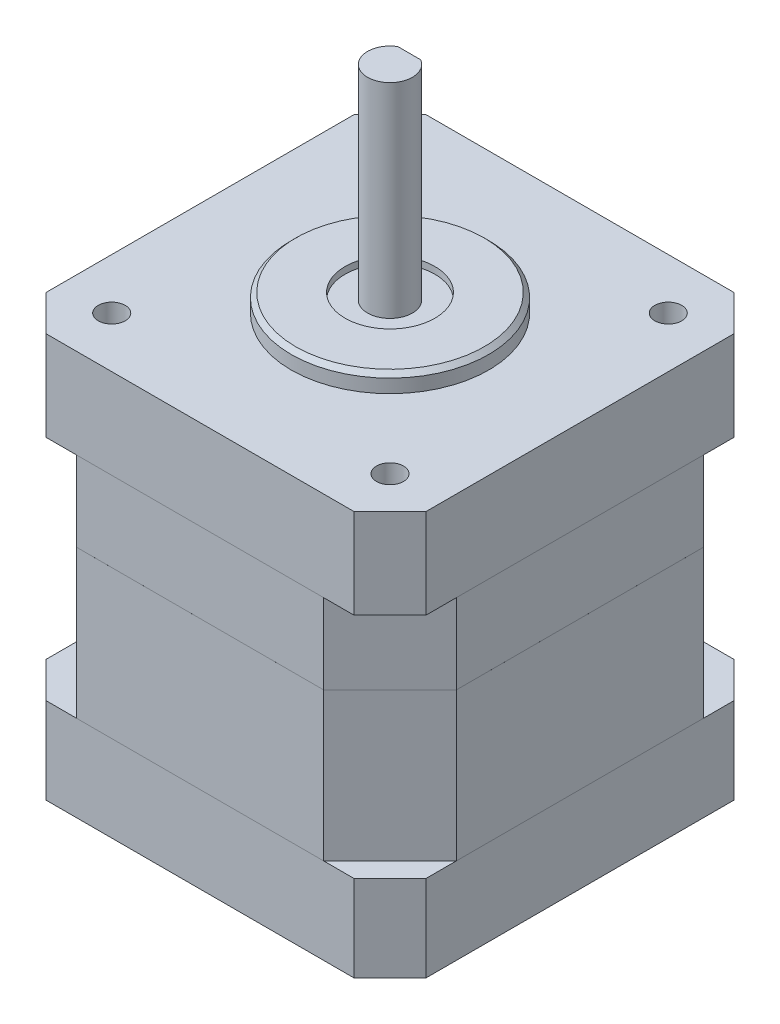
SolidWorks part; units mm, degrees
ref_plane "Front" through (0, 0, 0) normal (0, 0, 1) x (1, 0, 0)
ref_plane "Top" through (0, 0, 0) normal (0, 1, 0) x (1, 0, 0)
ref_plane "Right" through (0, 0, 0) normal (1, 0, 0) x (0, 0, -1)
sketch "Sketch1" plane through (0, 0, 0) normal (0, 1, 0) x (1, 0, 0)
  line L1 (-21.15, 21.15) -> (21.15, 21.15)
  line L2 (-21.15, 21.15) -> (-21.15, -21.15)
  line L3 (-21.15, -21.15) -> (21.15, -21.15)
  line L4 (21.15, 21.15) -> (21.15, -21.15)
  line L7 (0, 20) -> (0, -20) construction
  line L8 (20, 0) -> (-20, 0) construction
  line L10 (-55, 0) -> (55, 0) construction
  line L11 (0, -55) -> (0, 55) construction
  dimension "D1" = 42.3
extrude "Extrude1" add sketch "Sketch1" along normal blind 9.6 from offset 17 offset against normal yes
chamfer "Chamfer3" distance 4 angle 45 4 edges at (21.15, -12.2, 21.15) (-21.15, -12.2, 21.15) (21.15, -12.2, -21.15) (-21.15, -12.2, -21.15)
sketch "Sketch31" plane through (0, -7.4, 0) normal (0, 1, 0) x (1, 0, 0)
  line L0 (0, 21.15) -> (-13.75, 21.15) construction
  line L1 (17.15, 21.15) -> (-17.15, 21.15) construction
  line L2 (-13.75, 21.15) -> (13.75, 21.15)
  line L3 (-13.75, 21.15) -> (-21.15, 13.75)
  line L4 (-21.15, 17.15) -> (-21.15, -17.15) construction
  line L5 (13.75, 21.15) -> (21.15, 13.75)
  line L6 (21.15, -17.15) -> (21.15, 17.15) construction
  line L7 (-21.15, 0) -> (21.15, 0) construction
  line L8 (0, -21.15) -> (-13.75, -21.15) construction
  line L9 (13.75, -21.15) -> (21.15, -13.75)
  line L10 (-13.75, -21.15) -> (-21.15, -13.75)
  line L11 (-13.75, -21.15) -> (13.75, -21.15)
  line L12 (-21.15, 13.75) -> (-21.15, -13.75)
  line L13 (21.15, 13.75) -> (21.15, -13.75)
  dimension "D1" = 13.75
  dimension "D2" = 27.5
  dimension "D3" = 10.4652
extrude "Boss-Extrude8" add sketch "Sketch31" along normal blind 16.5
sketch "Sketch32" plane through (0, 9.1, 0) normal (0, 1, 0) x (1, 0, 0)
  line L0 (-17.15, 21.15) -> (-21.15, 17.15) construction
  line L1 (-13.75, 21.15) -> (-17.15, 21.15) construction
  line L2 (13.75, 21.15) -> (-13.75, 21.15) construction
  line L3 (17.15, 21.15) -> (13.75, 21.15) construction
  line L4 (21.15, 17.15) -> (17.15, 21.15) construction
  line L5 (21.15, 13.75) -> (21.15, 17.15) construction
  line L6 (21.15, -13.75) -> (21.15, 13.75) construction
  line L7 (-21.15, 17.15) -> (-21.15, 13.75) construction
  line L8 (-21.15, 13.75) -> (-21.15, -13.75) construction
  line L9 (21.15, -17.15) -> (21.15, -13.75) construction
  line L10 (17.15, -21.15) -> (21.15, -17.15) construction
  line L11 (13.75, -21.15) -> (17.15, -21.15) construction
  line L12 (-13.75, -21.15) -> (13.75, -21.15) construction
  line L13 (-17.15, -21.15) -> (-13.75, -21.15) construction
  line L14 (-21.15, -17.15) -> (-17.15, -21.15) construction
  line L15 (-21.15, -13.75) -> (-21.15, -17.15) construction
  line L16 (-17.15, 21.15) -> (-21.15, 17.15)
  line L17 (-13.75, 21.15) -> (-17.15, 21.15)
  line L18 (13.75, 21.15) -> (-13.75, 21.15)
  line L19 (17.15, 21.15) -> (13.75, 21.15)
  line L20 (21.15, 17.15) -> (17.15, 21.15)
  line L21 (21.15, 13.75) -> (21.15, 17.15)
  line L22 (21.15, -13.75) -> (21.15, 13.75)
  line L23 (-21.15, 17.15) -> (-21.15, 13.75)
  line L24 (-21.15, 13.75) -> (-21.15, -13.75)
  line L25 (21.15, -17.15) -> (21.15, -13.75)
  line L26 (17.15, -21.15) -> (21.15, -17.15)
  line L27 (13.75, -21.15) -> (17.15, -21.15)
  line L28 (-13.75, -21.15) -> (13.75, -21.15)
  line L29 (-17.15, -21.15) -> (-13.75, -21.15)
  line L30 (-21.15, -17.15) -> (-17.15, -21.15)
  line L31 (-21.15, -13.75) -> (-21.15, -17.15)
extrude "Boss-Extrude9" add sketch "Sketch32" along normal blind 7.65
sketch "Sketch33" plane through (0, 16.75, 0) normal (0, 1, 0) x (1, 0, 0)
  line L0 (-19.15, 19.15) -> (19.15, -19.15) construction
  line L1 (-17.15, 21.15) -> (-21.15, 17.15) construction
  line L2 (17.15, -21.15) -> (21.15, -17.15) construction
  circle A0 centre (0, 0) radius 11
  dimension "D1" = 22
extrude "Boss-Extrude10" add sketch "Sketch33" along normal blind 2
sketch "Sketch34" plane through (0, 18.75, 0) normal (0, 1, 0) x (1, 0, 0)
  circle A0 centre (0, 0) radius 5
  dimension "D1" = 10
extrude "Cut-Extrude1" cut sketch "Sketch34" against normal blind 2
sketch "Sketch35" plane through (0, 16.75, 0) normal (0, 1, 0) x (1, 0, 0)
  circle A0 centre (0, 0) radius 2.5
  dimension "D1" = 5
extrude "Boss-Extrude11" add sketch "Sketch35" along normal blind 20
sketch "Sketch36" plane through (0, 36.75, 0) normal (0, 1, 0) x (1, 0, 0)
  line L0 (0, -2.5) -> (0, 2.15)
  line L1 (-1.2757, 2.15) -> (1.2757, 2.15)
  circle A0 centre (0, 0) radius 2.5 construction
  circle A1 centre (0, 0) radius 2.5 construction
  circle A2 centre (0, 0) radius 2.5
  circle M1 centre (0, 0) radius 2.5
  dimension "D1" = 4.65
extrude "Cut-Extrude3" cut sketch "Sketch36" against normal blind 15 contours L1 M1 region at (0, 36.75, -2.2909)
sketch "Sketch37" plane through (21.15, 0, 0) normal (1, 0, 0) x (0, 0, -1)
  line L0 (-13.75, 9.1) -> (13.75, 9.1)
  line L1 (13.75, 9.1) -> (13.75, -7.4)
  line L2 (13.75, -7.4) -> (-13.75, -7.4)
  line L3 (-13.75, -7.4) -> (-13.75, 9.1)
extrude "Boss-Extrude12" add sketch "Sketch37" along normal blind 0.001
sketch "Sketch38" plane through (0, 0, 21.15) normal (0, 0, 1) x (1, 0, 0)
  line L1 (-13.75, 9.1) -> (13.75, 9.1)
  line L2 (-13.75, 9.1) -> (-13.75, -7.4)
  line L3 (-13.75, -7.4) -> (13.75, -7.4)
  line L4 (13.75, 9.1) -> (13.75, -7.4)
extrude "Boss-Extrude13" add sketch "Sketch38" along normal blind 0.001
sketch "Sketch39" plane through (-21.15, 0, 0) normal (-1, 0, 0) x (0, 0, 1)
  line L1 (-13.75, 9.1) -> (13.75, 9.1)
  line L2 (-13.75, 9.1) -> (-13.75, -7.4)
  line L3 (-13.75, -7.4) -> (13.75, -7.4)
  line L4 (13.75, 9.1) -> (13.75, -7.4)
extrude "Boss-Extrude14" add sketch "Sketch39" along normal blind 0.001
sketch "Sketch40" plane through (0, 0, -21.15) normal (0, 0, -1) x (-1, 0, 0)
  line L1 (-13.75, 9.1) -> (13.75, 9.1)
  line L2 (-13.75, 9.1) -> (-13.75, -7.4)
  line L3 (-13.75, -7.4) -> (13.75, -7.4)
  line L4 (13.75, 9.1) -> (13.75, -7.4)
extrude "Boss-Extrude15" add sketch "Sketch40" along normal blind 0.001
sketch "Sketch41" plane through (0, 16.75, 0) normal (0, 1, 0) x (1, 0, 0)
  line L0 (0, 21.15) -> (0, -21.15) construction
  line L1 (-21.15, 17.15) -> (-21.15, -17.15) construction
  line L2 (-21.15, 0) -> (-15.5, 0) construction
  line L3 (-15.5, 0) -> (-15.5, 15.5) construction
  line L4 (17.15, 21.15) -> (-17.15, 21.15) construction
  line L5 (-17.15, -21.15) -> (17.15, -21.15) construction
  circle A0 centre (-15.5, 15.5) radius 1.5
  circle A1 centre (-15.5, -15.5) radius 1.5
  circle A2 centre (15.5, -15.5) radius 1.5
  circle A3 centre (15.5, 15.5) radius 1.5
  dimension "D1" = 3
  dimension "D2" = 15.5
  dimension "D3" = 5.65
extrude "Cut-Extrude4" cut sketch "Sketch41" against normal blind 6
sketch "Sketch42" plane through (0, -17, 0) normal (0, -1, 0) x (1, 0, 0)
  circle A0 centre (0, 0) radius 4.5
  circle A1 centre (-15.5, 15.5) radius 1.5 construction
  circle A2 centre (15.5, 15.5) radius 1.5 construction
  circle A3 centre (15.5, -15.5) radius 1.5 construction
  circle A4 centre (-15.5, -15.5) radius 1.5 construction
  circle A5 centre (-15.5, 15.5) radius 1.5
  circle A6 centre (15.5, 15.5) radius 1.5
  circle A7 centre (15.5, -15.5) radius 1.5
  circle A8 centre (-15.5, -15.5) radius 1.5
  dimension "D1" = 9
extrude "Cut-Extrude5" cut sketch "Sketch42" against normal blind 3
sketch "Sketch43" plane through (0, -17, 0) normal (0, -1, 0) x (1, 0, 0)
  line L0 (0, 21.15) -> (8, 21.15) construction
  line L1 (-17.15, 21.15) -> (17.15, 21.15) construction
  line L3 (8, 21.15) -> (-8, 21.15)
  line L4 (8, 21.15) -> (8, 25.15)
  line L5 (8, 25.15) -> (-8, 25.15)
  line L6 (-8, 21.15) -> (-8, 25.15)
  dimension "D1" = 8
  dimension "D2" = 16
  dimension "D3" = 4
extrude "Boss-Extrude16" add sketch "Sketch43" against normal blind 3.2
sketch "Sketch44" plane through (0, 0, 21.15) normal (0, 0, 1) x (1, 0, 0)
  line L1 (8, -13.8) -> (-8, -13.8)
  line L2 (8, -13.8) -> (8, -7.4)
  line L3 (8, -7.4) -> (-8, -7.4)
  line L4 (-8, -13.8) -> (-8, -7.4)
  dimension "D1" = 16
  dimension "D2" = 6.4
extrude "Boss-Extrude17" add sketch "Sketch44" along normal blind 6
sketch "Sketch45" plane through (0, 0, 27.15) normal (0, 0, 1) x (1, 0, 0)
  line L0 (-8, -7.4) -> (-7.5, -7.4) construction
  line L1 (8, -7.4) -> (-8, -7.4) construction
  line L2 (-7.5, -7.4) -> (-7.5, -7.9) construction
  line L4 (-7.5, -7.9) -> (7.5, -7.9)
  line L5 (-7.5, -7.9) -> (-7.5, -13.4)
  line L6 (-7.5, -13.4) -> (7.5, -13.4)
  line L7 (7.5, -7.9) -> (7.5, -13.4)
  dimension "D1" = 0.5
  dimension "D2" = 0.5
  dimension "D3" = 5.5
  dimension "D4" = 15
extrude "Cut-Extrude6" cut sketch "Sketch45" against normal blind 5
sketch "Sketch46" plane through (0, 10.75, 0) normal (0, 1, 0) x (1, 0, 0)
  circle A0 centre (-15.5, -15.5) radius 1.5
  circle A1 centre (-15.5, 15.5) radius 1.5 construction
  circle A2 centre (15.5, 15.5) radius 1.5 construction
  circle A3 centre (15.5, -15.5) radius 1.5 construction
  circle A4 centre (-15.5, 15.5) radius 1.5
  circle A5 centre (15.5, 15.5) radius 1.5
  circle A6 centre (15.5, -15.5) radius 1.5
extrude "Boss-Extrude18" add sketch "Sketch46" along normal blind 1.5
chamfer "Chamfer4" distance 0.4 angle 45 1 edges at (0, 18.75, 11)
sketch "草图2" plane through (0, 36.75, 0) normal (0, 1, 0) x (1, 0, 0)
  line L0 (-1.2757, 2.15) -> (1.2757, 2.15)
  line L1 (-1.2757, 2.15) -> (1.2757, 2.15) construction
  circle A0 centre (0, 0) radius 2.5
  line M1 (1.2757, 2.15) -> (-1.2757, 2.15)
  arc M2 (-1.2757, 2.15) -> (1.2757, 2.15) centre (0, 0) ccw
extrude "凸台-拉伸1" add sketch "草图2" along normal blind 15.25 contours M2 M1 region at (0, 36.75, 0.0727)
sketch "草图3" plane through (0, 21.75, 0) normal (0, 1, 0) x (1, 0, 0)
  circle A0 centre (0, 0) radius 2.5
extrude "凸台-拉伸2" add sketch "草图3" along normal blind 11.25
sketch "草图4" plane through (0, 16.75, 0) normal (0, 1, 0) x (1, 0, 0)
  circle A0 centre (0, 0) radius 11
  circle A1 centre (0, 0) radius 5
extrude "凸台-拉伸3" add sketch "草图4" along normal blind 13.25
chamfer "倒角1" distance 0.5 angle 45 1 edges at (0, 30, 11)
sketch "草图5" plane through (0, 16.75, 0) normal (0, 1, 0) x (1, 0, 0)
  line L0 (-17.15, -21.15) -> (-21.15, -17.15)
  line L1 (-21.15, -17.15) -> (-21.15, 17.15)
  line L2 (-21.15, 17.15) -> (-17.15, 21.15)
  line L3 (-17.15, 21.15) -> (17.15, 21.15)
  line L4 (17.15, 21.15) -> (21.15, 17.15)
  line L5 (21.15, 17.15) -> (21.15, -17.15)
  line L6 (21.15, -17.15) -> (17.15, -21.15)
  line L7 (17.15, -21.15) -> (-17.15, -21.15)
  line L8 (0, 0) -> (-15.5, 0)
  line L9 (-15.5, 0) -> (-15.5, 15.5)
  line L10 (-15.5, 15.5) -> (15.5, 15.5)
  line L11 (15.5, 15.5) -> (15.5, -15.5)
  line L12 (15.5, -15.5) -> (-15.5, -15.5)
  line L13 (-15.5, -15.5) -> (-15.5, 0)
  circle A0 centre (-15.5, -15.5) radius 1.5
  circle A1 centre (-15.5, 15.5) radius 1.5
  circle A2 centre (15.5, 15.5) radius 1.5
  circle A3 centre (15.5, -15.5) radius 1.5
  circle A4 centre (-15.5, -15.5) radius 1.5 construction
  circle A5 centre (15.5, -15.5) radius 1.5 construction
  circle A6 centre (-15.5, 15.5) radius 1.5 construction
  line M5 (17.15, 21.15) -> (-17.15, 21.15)
  line M6 (-17.15, 21.15) -> (-21.15, 17.15)
  line M7 (-21.15, 17.15) -> (-21.15, -17.15)
  line M8 (-21.15, -17.15) -> (-17.15, -21.15)
  line M9 (-17.15, -21.15) -> (17.15, -21.15)
  line M10 (17.15, -21.15) -> (21.15, -17.15)
  line M11 (21.15, -17.15) -> (21.15, 17.15)
  line M12 (21.15, 17.15) -> (17.15, 21.15)
  circle M13 centre (0, 0) radius 11
  dimension "D1" = 3
  dimension "D2" = 3
  dimension "D3" = 3
  dimension "D4" = 3
extrude "凸台-拉伸4" add sketch "草图5" along normal blind 11.25 contours A3 L12 A0 L13 L9 A1 L10 A2 L11 M12 M5 M6 M7 M8 M9 M10 M11 | A3 L11 A2 L10 A1 L9 L13 A0 L12 M13 region at (-18.727, 16.75, 18.727) region at (-15.0616, 16.75, -7)
sketch "草图8" plane through (0, 9.1, 0) normal (0, -1, 0) x (1, 0, 0)
  line L0 (-17.15, 21.15) -> (-21.15, 17.15)
  line L1 (-21.15, 17.15) -> (-21.15, -17.15)
  line L2 (-21.15, -17.15) -> (-17.15, -21.15)
  line L3 (-17.15, -21.15) -> (17.15, -21.15)
  line L4 (17.15, -21.15) -> (21.15, -17.15)
  line L5 (21.15, -17.15) -> (21.15, 17.15)
  line L6 (21.15, 17.15) -> (17.15, 21.15)
  line L7 (17.15, 21.15) -> (-17.15, 21.15)
extrude "切除-拉伸1" cut sketch "草图8" against normal blind 8.9
sketch "草图12" plane through (0, 9.1, 0) normal (0, 1, 0) x (1, 0, 0)
  line L0 (21.15, -13.75) -> (13.75, -21.151)
  line L1 (13.75, -21.151) -> (-13.75, -21.15)
  line L2 (-13.75, -21.15) -> (-21.15, -13.75)
  line L3 (-21.15, -13.75) -> (-21.151, 13.75)
  line L4 (-21.151, 13.75) -> (-13.75, 21.15)
  line L5 (-13.75, 21.15) -> (13.75, 21.151)
  line L6 (13.75, 21.151) -> (21.151, 13.75)
  line L7 (21.151, 13.75) -> (21.15, -13.75)
extrude "凸台-拉伸8" add sketch "草图12" along normal blind 8.9
sketch "草图13" plane through (0, -17, 0) normal (0, -1, 0) x (1, 0, 0)
  circle A0 centre (-15.5, 15.5) radius 1.5
  circle A1 centre (15.5, 15.5) radius 1.5
  circle A2 centre (0, 0) radius 4.5
  circle A3 centre (-15.5, -15.5) radius 1.5
  circle A4 centre (15.5, -15.5) radius 1.5
extrude "凸台-拉伸11" add sketch "草图13" against normal blind 8.9
sketch "草图14" plane through (0, -17, 0) normal (0, -1, 0) x (1, 0, 0)
  line L0 (0, 0) -> (0, 15)
  line L1 (0, 15) -> (-15, 15)
  line L2 (-15, 15) -> (-15, -15)
  line L3 (-15, -15) -> (15, -15)
  line L4 (15, -15) -> (15, 15)
  circle A0 centre (0, 0) radius 4.5
  circle A1 centre (-15, 15) radius 3
  circle A2 centre (15, 15) radius 3
  circle A3 centre (-15, -15) radius 3
  circle A4 centre (15, -15) radius 3
extrude "切除-拉伸4" cut sketch "草图14" against normal blind 8.9 contours L1 A1 L2 | L2 A1 L1 | A2 | A0 | L2 A3 L3 | L3 A3 L2 | L4 A4 L3 | L3 A4 L4 region at (12.9387, -17, 17.0613) region at (13.7268, -17, -13.7268) region at (15.4244, -17, -15.4244) region at (-13.7268, -17, -13.7268) region at (-15.4244, -17, -15.4244) region at (-13.7268, -17, 13.7268) region at (-15.4244, -17, 15.4244) region at (3.092, -17, 3.092)
sketch "草图15" plane through (0, 18, 0) normal (0, 1, 0) x (1, 0, 0)
  circle A0 centre (0, 0) radius 5
extrude "凸台-拉伸12" add sketch "草图15" along normal blind 11.25
sketch "草图16" plane through (-8, 0, 0) normal (-1, 0, 0) x (0, 0, 1)
  line L1 (21.15, -17) -> (27.15, -17)
  line L2 (21.15, -17) -> (21.15, -7.4)
  line L3 (21.15, -7.4) -> (27.15, -7.4)
  line L4 (27.15, -17) -> (27.15, -7.4)
extrude "切除-拉伸5" cut sketch "草图16" against normal up to next
sketch "草图17" plane through (0, 28, 0) normal (0, 1, 0) x (1, 0, 0)
  line L0 (-21.15, 17.15) -> (-21.15, -17.15) construction
  line L1 (-17.15, -21.15) -> (17.15, -21.15) construction
  circle A0 centre (0, 0) radius 11 construction
  circle A1 centre (15, -15) radius 3 construction
  point P0 (15.5, -15.5)
  point P2 (-15.5, -15.5)
  point P9 (-15.5, 15.5)
  dimension "D1" = 31
  dimension "D2" = 5.65
  dimension "D3" = 5.65
  dimension "D4" = 31
